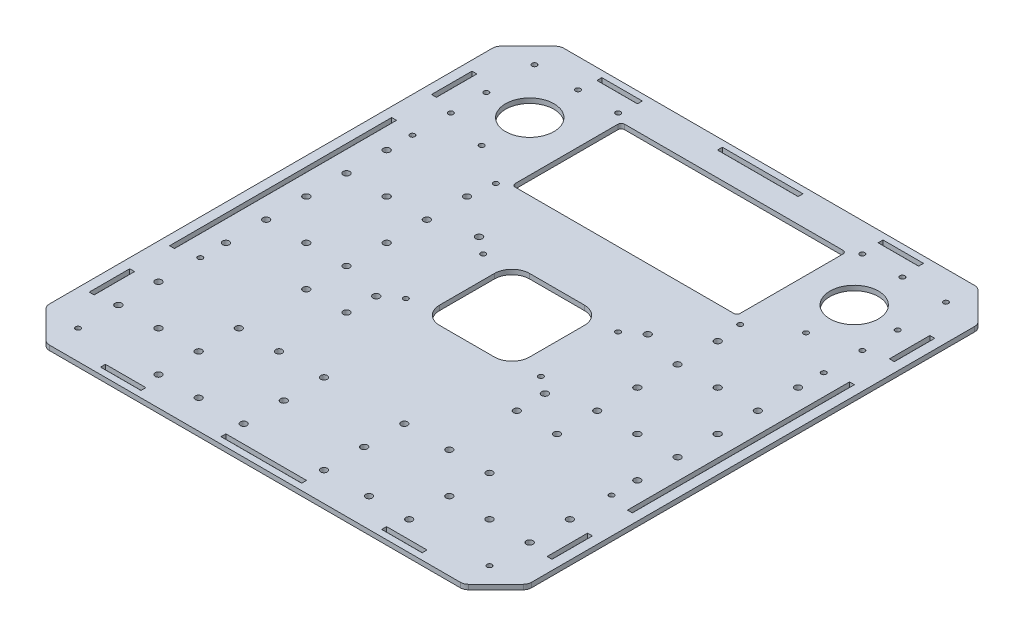
SolidWorks part; units mm, degrees
ref_plane "Front Plane" through (0, 0, 0) normal (0, 0, 1) x (1, 0, 0)
ref_plane "Top Plane" through (0, 0, 0) normal (0, 1, 0) x (1, 0, 0)
ref_plane "Right Plane" through (0, 0, 0) normal (1, 0, 0) x (0, 0, -1)
sketch "Sketch1" plane through (0, 0, 0) normal (0, 1, 0) x (1, 0, 0)
  line L0 (0, 0) -> (16.6467, 0) construction
  line L1 (0, 0) -> (0, 19.1715) construction
  line L3 (150, 137.9289) -> (150, 56)
  line L4 (144, 54) -> (78, 54) construction
  line L7 (32, -50) -> (68, -50) construction
  line L8 (32, -50) -> (32, 50) construction
  line L9 (32, 50) -> (68, 50) construction
  line L10 (68, -50) -> (68, 50) construction
  line L11 (32, -50) -> (68, 50) construction
  line L12 (32, 50) -> (68, -50) construction
  line L20 (131.4645, 158.5355) -> (148.5355, 141.4645)
  line L21 (78, 54) -> (78, -54) construction
  line L23 (127.9289, 160) -> (-127.9289, 160)
  line L24 (144, -54) -> (78, -54) construction
  line L25 (150, -137.9289) -> (150, -56)
  line L26 (131.4645, -158.5355) -> (148.5355, -141.4645)
  line L27 (127.9289, -160) -> (-127.9289, -160)
  line L28 (-131.4645, 158.5355) -> (-148.5355, 141.4645)
  line L29 (-150, 137.9289) -> (-150, 56)
  line L33 (-150, -137.9289) -> (-150, -56)
  line L34 (-131.4645, -158.5355) -> (-148.5355, -141.4645)
  line L35 (144, 54) -> (144, -54) construction
  line L36 (150, 56) -> (150, -56)
  line L37 (-144, 54) -> (-144, -54) construction
  line L38 (-144, 54) -> (-78, 54) construction
  line L40 (-78, 54) -> (-78, -54) construction
  line L41 (-150, 56) -> (-150, -56)
  line L42 (-144, -54) -> (-78, -54) construction
  circle A5 centre (52.5, 32) radius 2.075
  circle A7 centre (52.5, -32) radius 2.075
  circle A8 centre (-52.5, -32) radius 2.075
  circle A9 centre (-52.5, 32) radius 2.075
  arc A10 (131.4645, -158.5355) -> (127.9289, -160) centre (127.9289, -155) cw
  arc A11 (150, -137.9289) -> (148.5355, -141.4645) centre (145, -137.9289) cw
  arc A12 (-131.4645, -158.5355) -> (-127.9289, -160) centre (-127.9289, -155) ccw
  arc A13 (-150, -137.9289) -> (-148.5355, -141.4645) centre (-145, -137.9289) ccw
  arc A18 (148.5355, 141.4645) -> (150, 137.9289) centre (145, 137.9289) cw
  arc A19 (131.4645, 158.5355) -> (127.9289, 160) centre (127.9289, 155) ccw
  arc A20 (-148.5355, 141.4645) -> (-150, 137.9289) centre (-145, 137.9289) ccw
  arc A21 (-131.4645, 158.5355) -> (-127.9289, 160) centre (-127.9289, 155) cw
  circle A22 centre (0, 0) radius 145 construction
  circle A23 centre (-98, 106.8691) radius 38 construction
  circle A24 centre (98, 106.8691) radius 38 construction
  circle A25 centre (-98, -106.8691) radius 38 construction
  circle A26 centre (98, -106.8691) radius 38 construction
  point P17 (50, 0)
  point P31 (78, 0)
  point P33 (78, 0)
  point P38 (0, 150)
  point P41 (0, 160)
  point P43 (0, -150)
  point P50 (0, -160)
  point P52 (130, -160)
  point P55 (150, -140)
  point P58 (-130, -160)
  point P61 (-150, -140)
  point P64 (-150, -54)
  point P67 (-150, 54)
  point P70 (150, 54)
  point P73 (150, -54)
  point P76 (150, 140)
  point P79 (130, 160)
  point P82 (-150, 140)
  point P85 (-130, 160)
  dimension "D2" = 290
  dimension "D3" = 160
  dimension "D9" = 15.5
  dimension "D10" = 32
  dimension "D11" = 4.15
  dimension "D12" = 10
  dimension "D15" = 5
  dimension "D16" = 76
  dimension "D17" = 98
  dimension "D19" = 6
  dimension "D4" = 150
  dimension "D5" = 54
  dimension "D6" = 32
  dimension "D7" = 100
  dimension "D8" = 36
  dimension "D13" = 135
  dimension "D14" = 20
base flange "Base-Flange1" sketch "Sketch1" thickness 3 reverse thickness direction no parameters "D1"=0.7366
sketch "Sketch6" plane through (0, 0, 0) normal (0, 1, 0) x (1, 0, 0)
  line L0 (0, 0) -> (17.8088, 0) construction
  line L1 (0, 0) -> (0, 40.1375) construction
  line L2 (74.9, 156) -> (74.9, 152.95)
  line L3 (133.5, 54) -> (133.5, -54) construction
  line L4 (144, 54) -> (144, -54)
  line L6 (-17, -28) -> (17, -28)
  line L7 (140.95, 53.9) -> (140.95, 69.1)
  line L8 (140.95, 69.1) -> (144, 69.1)
  line L9 (144, 69.1) -> (144, 54)
  line L11 (140.95, 119.1) -> (140.95, 93.9)
  line L12 (140.95, 93.9) -> (144, 93.9)
  line L13 (144, 93.9) -> (144, 119.1)
  line L14 (144, 119.1) -> (140.95, 119.1)
  line L15 (74.9, 152.95) -> (100.1, 152.95)
  line L16 (100.1, 152.95) -> (100.1, 156)
  line L17 (-25.1, 156) -> (25.1, 156)
  line L18 (25.1, 156) -> (25.1, 152.95)
  line L19 (25.1, 152.95) -> (-25.1, 152.95)
  line L20 (100.1, 156) -> (74.9, 156)
  line L21 (127.9289, 160) -> (-127.9289, 160) construction
  line L22 (-25.1, 156) -> (-25.1, 152.95)
  line L23 (150, -137.9289) -> (150, 137.9289) construction
  line L24 (-100.1, 152.95) -> (-100.1, 156)
  line L25 (-74.9, 152.95) -> (-100.1, 152.95)
  line L26 (-74.9, 156) -> (-74.9, 152.95)
  line L27 (-100.1, 156) -> (-74.9, 156)
  line L28 (-144, 69.1) -> (-144, 54)
  line L29 (-140.95, 69.1) -> (-144, 69.1)
  line L30 (-140.95, 53.9) -> (-140.95, 69.1)
  line L32 (-144, 93.9) -> (-144, 119.1)
  line L33 (-140.95, 93.9) -> (-144, 93.9)
  line L34 (-140.95, 119.1) -> (-140.95, 93.9)
  line L35 (-144, 119.1) -> (-140.95, 119.1)
  line L36 (-140.95, -69.1) -> (-144, -69.1)
  line L37 (-140.95, -53.9) -> (-140.95, -69.1)
  line L39 (-144, -69.1) -> (-144, -54)
  line L40 (-140.95, -93.9) -> (-144, -93.9)
  line L41 (-140.95, -119.1) -> (-140.95, -93.9)
  line L42 (-144, -119.1) -> (-140.95, -119.1)
  line L43 (-144, -93.9) -> (-144, -119.1)
  line L44 (144, -69.1) -> (144, -54)
  line L45 (140.95, -69.1) -> (144, -69.1)
  line L46 (140.95, -53.9) -> (140.95, -69.1)
  line L48 (144, -93.9) -> (144, -119.1)
  line L49 (140.95, -93.9) -> (144, -93.9)
  line L50 (140.95, -119.1) -> (140.95, -93.9)
  line L51 (144, -119.1) -> (140.95, -119.1)
  line L52 (100.1, -152.95) -> (100.1, -156)
  line L53 (74.9, -152.95) -> (100.1, -152.95)
  line L54 (74.9, -156) -> (74.9, -152.95)
  line L55 (100.1, -156) -> (74.9, -156)
  line L56 (-74.9, -152.95) -> (-100.1, -152.95)
  line L57 (-74.9, -156) -> (-74.9, -152.95)
  line L58 (-100.1, -156) -> (-74.9, -156)
  line L59 (-100.1, -152.95) -> (-100.1, -156)
  line L60 (25.1, -156) -> (25.1, -152.95)
  line L61 (-25.1, -156) -> (25.1, -156)
  line L62 (-25.1, -156) -> (-25.1, -152.95)
  line L63 (25.1, -152.95) -> (-25.1, -152.95)
  line L64 (-28, -17) -> (-28, 17)
  line L65 (140.95, 53.9) -> (140.95, -53.9)
  line L66 (-140.95, 53.9) -> (-140.95, -53.9)
  line L67 (-144, 54) -> (-144, -54)
  line L68 (150, -137.9289) -> (150, 137.9289) construction
  line L69 (-17, 28) -> (17, 28)
  line L70 (28, -17) -> (28, 17)
  line L71 (-28, -28) -> (28, 28) construction
  line L72 (-28, 28) -> (28, -28) construction
  circle A1 centre (0, 0) radius 145 construction
  circle A2 centre (128, 142) radius 1.55
  circle A3 centre (-60, 132) radius 1.55 construction
  circle A4 centre (-128, 142) radius 1.55
  circle A5 centre (128, 78) radius 1.55 construction
  circle A8 centre (60, 132) radius 1.55 construction
  circle A9 centre (-128, -142) radius 1.55
  circle A10 centre (128, -78) radius 1.55 construction
  circle A11 centre (128, -142) radius 1.55
  circle A12 centre (0, 60) radius 1.55 construction
  circle A13 centre (0, -60) radius 1.55 construction
  circle A14 centre (60, -132) radius 1.55 construction
  circle A15 centre (-60, -132) radius 1.55 construction
  circle A16 centre (-128, 78) radius 1.55 construction
  circle A17 centre (-128, -78) radius 1.55 construction
  circle A18 centre (52.5, 32) radius 2.075 construction
  circle A19 centre (0, 0) radius 26 construction
  arc A20 (-17, -28) -> (-28, -17) centre (-17, -17) cw
  arc A21 (17, -28) -> (28, -17) centre (17, -17) ccw
  arc A22 (17, 28) -> (28, 17) centre (17, 17) cw
  arc A23 (-28, 17) -> (-17, 28) centre (-17, 17) cw
  circle A24 centre (42, 24) radius 1.55
  circle A25 centre (42, -24) radius 1.55
  circle A26 centre (-42, 24) radius 1.55
  circle A27 centre (-42, -24) radius 1.55
  circle A28 centre (-128, -66) radius 1.55
  circle A29 centre (128, -66) radius 1.55
  circle A30 centre (128, 66) radius 1.55
  circle A31 centre (-128, 66) radius 1.55
  circle A32 centre (-128, 90) radius 1.55
  circle A33 centre (128, 90) radius 1.55
  point P47 (0, 152.95)
  point P48 (0, 156)
  dimension "D2" = 290
  dimension "D3" = 3.05
  dimension "D13" = 18
  dimension "D14" = 3.1
  dimension "D15" = 64
  dimension "D16" = 28
  dimension "D17" = 22
  dimension "D12" = 68
  dimension "D18" = 72
  dimension "D19" = 6
  dimension "D4" = 81
  dimension "D5" = 52
  dimension "D23" = 11
  dimension "D24" = 24
  dimension "D25" = 42
  dimension "D26" = 3.1
  dimension "D27" = 76
  dimension "D28" = 52
  dimension "D6" = 25.2
  dimension "D7" = 24.8
  dimension "D8" = 25.2
  dimension "D9" = 25.1
  dimension "D10" = 49.8
  dimension "D11" = 4
  dimension "D20" = 69.1
  dimension "D21" = 56
  dimension "D22" = 56
extrude "Cut-Extrude1" cut sketch "Sketch6" against normal blind 10 normal cut yes
sketch "Sketch7" plane through (0, 0, 0) normal (0, 1, 0) x (1, 0, 0)
  line L0 (0, 0) -> (15.8505, 0) construction
  line L1 (0, 0) -> (0, 23.9668) construction
  line L2 (127.9289, 160) -> (-127.9289, 160) construction
  line L3 (-68, 70) -> (68, 70)
  line L4 (-70, 72) -> (-70, 136)
  line L5 (-68, 138) -> (68, 138)
  line L6 (70, 72) -> (70, 136)
  line L7 (-70, 70) -> (70, 138) construction
  line L8 (-70, 138) -> (70, 70) construction
  line L10 (0, 0) -> (-128, 142) construction
  arc A0 (68, 138) -> (70, 136) centre (68, 136) cw
  arc A1 (68, 70) -> (70, 72) centre (68, 72) ccw
  arc A2 (-68, 70) -> (-70, 72) centre (-68, 72) cw
  arc A3 (-70, 136) -> (-68, 138) centre (-68, 136) cw
  circle A4 centre (76, 142) radius 1.55
  circle A5 centre (76, 66) radius 1.55
  circle A6 centre (-76, 142) radius 1.55
  circle A7 centre (-76, 66) radius 1.55
  circle A8 centre (-100.9577, 112) radius 15.05
  circle A10 centre (100.9577, 112) radius 15.05
  circle A62 centre (-100.9577, 64) radius 15.05 construction
  circle A63 centre (100.9577, 64) radius 15.05 construction
  circle A73 centre (100.9577, 142) radius 1.55
  circle A74 centre (100.9577, 82) radius 1.55
  circle A75 centre (128, 112) radius 1.55
  circle A78 centre (-100.9577, 142) radius 1.55
  circle A79 centre (-100.9577, 82) radius 1.55
  circle A80 centre (-128, 112) radius 1.55
  point P4 (0, 104)
  dimension "D4" = 2
  dimension "D5" = 76
  dimension "D6" = 38
  dimension "D7" = 3.1
  dimension "D8" = 38
  dimension "D9" = 30.1
  dimension "D10" = 48
  dimension "D11" = 58
  dimension "D12" = 30
  dimension "D13" = 30
  dimension "D31" = 48
  dimension "D1" = 140
  dimension "D2" = 68
  dimension "D3" = 22
extrude "Cut-Extrude2" cut sketch "Sketch7" against normal blind 10 normal cut yes
sketch "Sketch8" plane through (0, 0, 0) normal (0, 1, 0) x (1, 0, 0)
  line L0 (0, -15.217) -> (0, 20.4229) construction
  line L1 (17.9201, 0) -> (-23.1259, 0) construction
  circle A0 centre (-53, -50) radius 2.05
  circle A1 centre (-53, -142) radius 2.05
  circle A2 centre (-128, 50) radius 2.05
  circle A3 centre (-78, 50) radius 2.05
  circle A4 centre (-78, -142) radius 2.05
  circle A6 centre (-128, 0) radius 2.05
  circle A7 centre (-78, -25) radius 2.05
  circle A8 centre (-128, -92) radius 2.05
  circle A9 centre (-78, -92) radius 2.05
  circle A10 centre (-53, -92) radius 2.05
  circle A11 centre (-128, 66) radius 1.55 construction
  circle A12 centre (-128, 66) radius 1.55 construction
  circle A13 centre (-128, 25) radius 2.05
  circle A14 centre (-128, -25) radius 2.05
  circle A15 centre (-76, 66) radius 1.55 construction
  circle A16 centre (-76, 66) radius 1.55 construction
  circle A17 centre (-78, 25) radius 2.05
  circle A18 centre (-25, -92) radius 2.05
  circle A19 centre (-25, -142) radius 2.05
  circle A20 centre (-128, -50) radius 2.05
  circle A21 centre (53, -50) radius 2.05
  circle A22 centre (78, -50) radius 2.05
  circle A23 centre (-128, -142) radius 1.55 construction
  circle A24 centre (-128, -117) radius 2.05
  circle A25 centre (-103, -142) radius 2.05 construction
  circle A26 centre (-128, -142) radius 1.55 construction
  circle A27 centre (-103, -92) radius 2.05 construction
  circle A28 centre (-103, -50) radius 2.05 construction
  circle A29 centre (-103, -25) radius 2.05
  circle A30 centre (-103, 0) radius 2.05 construction
  circle A31 centre (-103, 25) radius 2.05
  circle A32 centre (-103, 50) radius 2.05 construction
  circle A33 centre (-78, 0) radius 2.05
  circle A34 centre (-78, -50) radius 2.05
  circle A35 centre (-25, -117) radius 2.05
  circle A36 centre (-103, -117) radius 2.05
  circle A37 centre (-78, -117) radius 2.05
  circle A38 centre (-53, -117) radius 2.05 construction
  circle A39 centre (78, 0) radius 2.05
  circle A40 centre (103, 50) radius 2.05 construction
  circle A41 centre (103, 25) radius 2.05
  circle A42 centre (103, 0) radius 2.05 construction
  circle A43 centre (103, -25) radius 2.05
  circle A44 centre (103, -50) radius 2.05 construction
  circle A45 centre (128, -50) radius 2.05
  circle A46 centre (78, 25) radius 2.05
  circle A47 centre (128, -25) radius 2.05
  circle A48 centre (128, 25) radius 2.05
  circle A49 centre (78, -25) radius 2.05
  circle A50 centre (128, 0) radius 2.05
  circle A51 centre (78, 50) radius 2.05
  circle A52 centre (128, 50) radius 2.05
  circle A53 centre (53, -117) radius 2.05 construction
  circle A54 centre (78, -117) radius 2.05
  circle A55 centre (103, -117) radius 2.05
  circle A56 centre (25, -117) radius 2.05
  circle A57 centre (103, -92) radius 2.05 construction
  circle A58 centre (103, -142) radius 2.05 construction
  circle A59 centre (128, -117) radius 2.05
  circle A60 centre (25, -142) radius 2.05
  circle A61 centre (25, -92) radius 2.05
  circle A62 centre (53, -92) radius 2.05
  circle A63 centre (78, -92) radius 2.05
  circle A64 centre (128, -92) radius 2.05
  circle A65 centre (78, -142) radius 2.05
  circle A66 centre (53, -142) radius 2.05
  dimension "D2" = 25
  dimension "D3" = 25
  dimension "D4" = 50
  dimension "D5" = 25
  dimension "D6" = 25
  dimension "D7" = 25
  dimension "D8" = 25
  dimension "D9" = 25
  dimension "D10" = 50
  dimension "D11" = 25
  dimension "D12" = 4.1
extrude "Cut-Extrude3" cut sketch "Sketch8" against normal blind 10 normal cut yes
sketch "Bend-Lines1" [suppressed] plane through (0, 0, 0) normal (0, 1, 0) x (1, 0, 0)
sketch "Bounding-Box1" [suppressed] plane through (0, 0, 0) normal (0, 1, 0) x (1, 0, 0)
sheet metal parameters "Sheet-Metal2" thickness 3 parameters "D1"=0.7366
flat pattern "Flat-Pattern2" [suppressed]
sketch "Bend-Lines2" plane through (0, 0, 0) normal (0, 1, 0) x (1, 0, 0)
sketch3d "Bounding-Box2" [suppressed]
  line L0 (22.0712, -4.9999, 0) -> (22.0711, 315, 0) construction
  line L1 (-277.9288, -5, 0) -> (-277.9289, 314.9999, 0) construction
  line L2 (22.0712, -4.9999, 0) -> (-277.9288, -5, 0) construction
  line L3 (22.0711, 315, 0) -> (-277.9289, 314.9999, 0) construction
sheet metal parameters "Sheet-Metal4" thickness 3 parameters "D1"=0.7366
flat pattern "Flat-Pattern2"
sketch "Bend-Lines2" plane through (0, 0, 0) normal (0, 1, 0) x (1, 0, 0)
sketch3d "Bounding-Box2" [suppressed]
  line L0 (22.0712, -4.9999, 0) -> (22.0711, 315, 0) construction
  line L1 (-277.9288, -5, 0) -> (-277.9289, 314.9999, 0) construction
  line L2 (22.0712, -4.9999, 0) -> (-277.9288, -5, 0) construction
  line L3 (22.0711, 315, 0) -> (-277.9289, 314.9999, 0) construction
sheet metal parameters "Sheet-Metal5" thickness 3 parameters "D1"=0.7366
flat pattern "Flat-Pattern2"
sketch "Bend-Lines2" plane through (0, 0, 0) normal (0, 1, 0) x (1, 0, 0)
sketch3d "Bounding-Box2" [suppressed]
  line L0 (22.0712, -4.9999, 0) -> (22.0711, 315, 0) construction
  line L1 (-277.9288, -5, 0) -> (-277.9289, 314.9999, 0) construction
  line L2 (22.0712, -4.9999, 0) -> (-277.9288, -5, 0) construction
  line L3 (22.0711, 315, 0) -> (-277.9289, 314.9999, 0) construction
sheet metal parameters "Sheet-Metal6" thickness 3 parameters "D1"=0.7366
flat pattern "Flat-Pattern2"
sketch "Bend-Lines2" plane through (0, 0, 0) normal (0, 1, 0) x (1, 0, 0)
sketch3d "Bounding-Box2" [suppressed]
  line L0 (22.0712, -4.9999, 0) -> (22.0711, 315, 0) construction
  line L1 (-277.9288, -5, 0) -> (-277.9289, 314.9999, 0) construction
  line L2 (22.0712, -4.9999, 0) -> (-277.9288, -5, 0) construction
  line L3 (22.0711, 315, 0) -> (-277.9289, 314.9999, 0) construction
